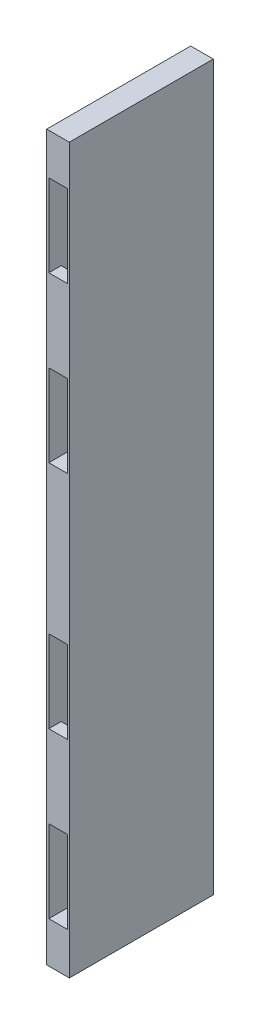
SolidWorks part; units mm, degrees
ref_plane "Top" through (0, 0, 0) normal (0, 0, 1) x (1, 0, 0)
ref_plane "Front" through (0, 0, 0) normal (0, 1, 0) x (1, 0, 0)
ref_plane "Right" through (0, 0, 0) normal (1, 0, 0) x (0, 0, -1)
sketch "Profile Sketch" plane through (0.0456, 0, -0.0242) normal (0, 1, 0) x (-1, 0, 0)
  line L0 (2.5456, -17.4758) -> (2.5456, 0.0242)
  line L1 (2.5456, 0.0242) -> (0.0456, 0.0242)
  line L2 (0.0456, 0.0242) -> (0.0456, -17.4758)
  line L3 (0.0456, -17.4758) -> (2.5456, -17.4758)
  line L12 (2.2956, 0.0242) -> (2.2956, -17.4758) construction
  dimension "D1" = 17.5
  dimension "D3" = 2.25
  dimension "Cover Thickness" = 0.25
extrude "Profile Extrude" add sketch "Profile Sketch" along normal blind 88
ref_plane "Mid Plane" through (0, 44, 0) normal (0, -1, 0) x (-1, 0, 0)
ref_plane "Right Cut Out Location" through (0, 20, 0) normal (0, -1, 0) x (-1, 0, 0)
ref_plane "Left Cut Out Location" through (0, 68, 0) normal (0, -1, 0) x (-1, 0, 0)
sketch "Cover Latch Cut Out Sketch" plane through (-2.5, 0, 0) normal (-1, 0, 0) x (0, 0, 1)
  line L0 (-17.5, 88) -> (-17.5, 0) construction
  line L4 (-17.5, 35) -> (-17.5, 5)
  line L5 (0, 15) -> (-1.5, 15)
  line L10 (0, 25) -> (0, 15) construction
  line L11 (0, 88) -> (0, 0) construction
  line L12 (-1.5, 15) -> (-2.1583, 20)
  line L13 (-2.1583, 20) -> (-1.5, 25)
  line L14 (-1.5, 25) -> (0, 25)
  line L15 (-2.1583, 20) -> (0, 20) construction
  line L16 (0, 25) -> (0, 35)
  line L17 (0, 35) -> (-17.5, 35)
  line L18 (0, 15) -> (0, 5)
  line L21 (0, 5) -> (-17.5, 5)
  point P3 (0, 44)
  dimension "D1" = 1.5
  dimension "D2" = 10
  dimension "D3" = 10
  dimension "D4" = 7.5
  dimension "Latch Position" = 24
extrude "Cover Latch Cut Out" cut sketch "Cover Latch Cut Out Sketch" against normal blind 2.25
mirror "Cover Latch Cut Out Mirror" about plane through (0, 44, 0) normal (0, -1, 0) of "Cover Latch Cut Out"
sketch "Side Cover Sketch" plane through (0, 0, 0) normal (0, 1, 0) x (1, 0, 0)
  line L7 (-2.75, 17.5) -> (-2.5, 17.5)
  line L8 (-2.75, 17.5) -> (-2.75, 0)
  line L9 (-2.75, 0) -> (-2.5, 0)
  line L10 (-2.5, 17.5) -> (-2.5, 0)
  dimension "Cover Thickness" = 0.25
extrude "Side Cover Extrude" add sketch "Side Cover Sketch" along normal through all
